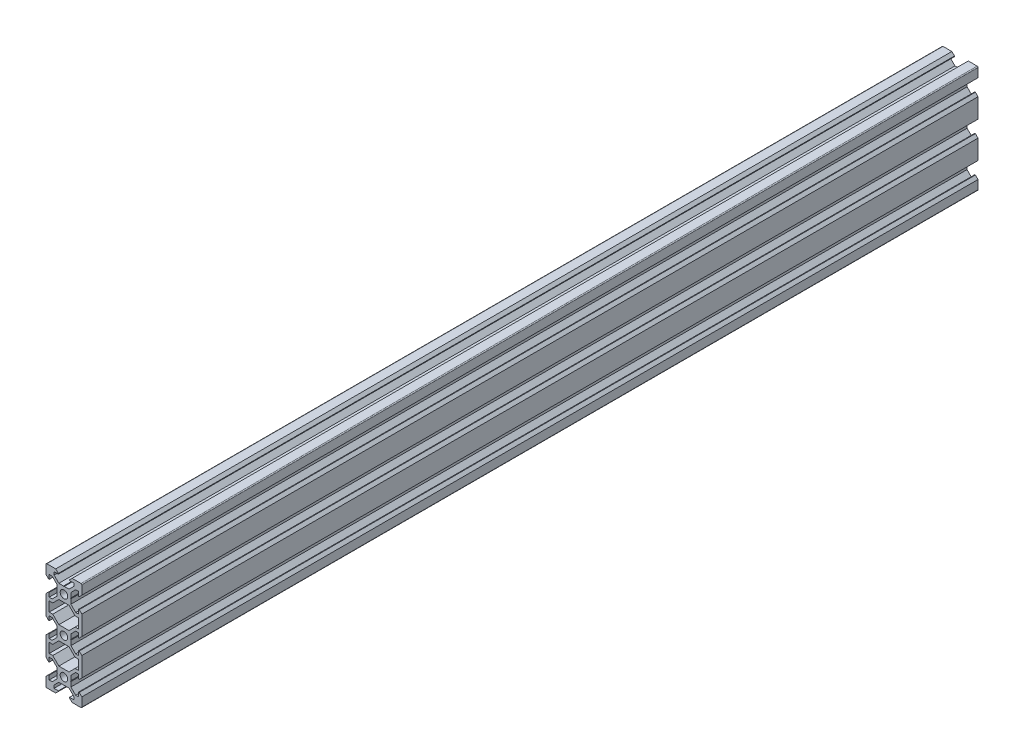
SolidWorks part; units mm, degrees
material "6061-T6 (SS)"
ref_plane "Front Plane" through (0, 0, 0) normal (0, 0, 1) x (1, 0, 0)
ref_plane "Top Plane" through (0, 0, 0) normal (0, 1, 0) x (1, 0, 0)
ref_plane "Right Plane" through (0, 0, 0) normal (1, 0, 0) x (0, 0, -1)
sketch "Sketch1" plane through (0, 0, 0) normal (0, 0, 1) x (1, 0, 0)
  line L0 (0, 0) -> (10, 0) construction
  line L1 (9.5, -30) -> (-9.5, -30)
  line L2 (10, -29.5) -> (10, 29.5)
  line L3 (9.5, 30) -> (-9.5, 30)
  line L4 (-10, -29.5) -> (-10, 29.5)
  line L5 (10, -30) -> (-10, 30) construction
  line L6 (10, 30) -> (-10, -30) construction
  circle A0 centre (0, 20) radius 2.1
  circle A1 centre (0, 0) radius 2.1
  circle A2 centre (0, -20) radius 2.1
  arc A3 (-9.5, -30) -> (-10, -29.5) centre (-9.5, -29.5) cw
  arc A4 (9.5, -30) -> (10, -29.5) centre (9.5, -29.5) ccw
  arc A5 (10, 29.5) -> (9.5, 30) centre (9.5, 29.5) ccw
  arc A6 (-9.5, 30) -> (-10, 29.5) centre (-9.5, 29.5) ccw
  point P0 (0, 0)
  line B0 (0, 20) -> (0, 30) construction
  line B1 (0, 23.69) -> (-0.21, 23.9)
  line B2 (-0.21, 23.9) -> (-2.8393, 23.9)
  line B3 (-2.8393, 23.9) -> (-5.5, 26.5607)
  line B4 (-5.5, 26.5607) -> (-5.5, 28.2)
  line B5 (-5.5, 28.2) -> (-3.125, 28.2)
  line B6 (-3.125, 28.2) -> (-3.125, 28.545)
  line B7 (-3.125, 28.545) -> (-4.58, 30)
  line B8 (-4.58, 30) -> (4.58, 30)
  line B9 (0, 20) -> (-5.9132, 25.9132) construction
  line B10 (3.125, 28.545) -> (4.58, 30)
  line B11 (3.125, 28.2) -> (3.125, 28.545)
  line B12 (5.5, 28.2) -> (3.125, 28.2)
  line B13 (5.5, 26.5607) -> (5.5, 28.2)
  line B14 (2.8393, 23.9) -> (5.5, 26.5607)
  line B15 (0.21, 23.9) -> (2.8393, 23.9)
  line B16 (0, 23.69) -> (0.21, 23.9)
  line B17 (0, 20) -> (-10, 20) construction
  line B18 (-3.69, 20) -> (-3.9, 19.79)
  line B19 (-3.9, 19.79) -> (-3.9, 17.1607)
  line B20 (-3.9, 17.1607) -> (-6.5607, 14.5)
  line B21 (-6.5607, 14.5) -> (-8.2, 14.5)
  line B22 (-8.2, 14.5) -> (-8.2, 16.875)
  line B23 (-8.2, 16.875) -> (-8.545, 16.875)
  line B24 (-8.545, 16.875) -> (-10, 15.42)
  line B25 (-10, 15.42) -> (-10, 24.58)
  line B26 (0, 20) -> (-5.9132, 14.0868) construction
  line B27 (-8.545, 23.125) -> (-10, 24.58)
  line B28 (-8.2, 23.125) -> (-8.545, 23.125)
  line B29 (-8.2, 25.5) -> (-8.2, 23.125)
  line B30 (-6.5607, 25.5) -> (-8.2, 25.5)
  line B31 (-3.9, 22.8393) -> (-6.5607, 25.5)
  line B32 (-3.9, 20.21) -> (-3.9, 22.8393)
  line B33 (-3.69, 20) -> (-3.9, 20.21)
  line B34 (0, 0) -> (-10, 0) construction
  line B35 (-3.69, 0) -> (-3.9, -0.21)
  line B36 (-3.9, -0.21) -> (-3.9, -2.8393)
  line B37 (-3.9, -2.8393) -> (-6.5607, -5.5)
  line B38 (-6.5607, -5.5) -> (-8.2, -5.5)
  line B39 (-8.2, -5.5) -> (-8.2, -3.125)
  line B40 (-8.2, -3.125) -> (-8.545, -3.125)
  line B41 (-8.545, -3.125) -> (-10, -4.58)
  line B42 (-10, -4.58) -> (-10, 4.58)
  line B43 (0, 0) -> (-5.9132, -5.9132) construction
  line B44 (-8.545, 3.125) -> (-10, 4.58)
  line B45 (-8.2, 3.125) -> (-8.545, 3.125)
  line B46 (-8.2, 5.5) -> (-8.2, 3.125)
  line B47 (-6.5607, 5.5) -> (-8.2, 5.5)
  line B48 (-3.9, 2.8393) -> (-6.5607, 5.5)
  line B49 (-3.9, 0.21) -> (-3.9, 2.8393)
  line B50 (-3.69, 0) -> (-3.9, 0.21)
  line B51 (0, -20) -> (-10, -20) construction
  line B52 (-3.69, -20) -> (-3.9, -20.21)
  line B53 (-3.9, -20.21) -> (-3.9, -22.8393)
  line B54 (-3.9, -22.8393) -> (-6.5607, -25.5)
  line B55 (-6.5607, -25.5) -> (-8.2, -25.5)
  line B56 (-8.2, -25.5) -> (-8.2, -23.125)
  line B57 (-8.2, -23.125) -> (-8.545, -23.125)
  line B58 (-8.545, -23.125) -> (-10, -24.58)
  line B59 (-10, -24.58) -> (-10, -15.42)
  line B60 (0, -20) -> (-5.9132, -25.9132) construction
  line B61 (-8.545, -16.875) -> (-10, -15.42)
  line B62 (-8.2, -16.875) -> (-8.545, -16.875)
  line B63 (-8.2, -14.5) -> (-8.2, -16.875)
  line B64 (-6.5607, -14.5) -> (-8.2, -14.5)
  line B65 (-3.9, -17.1607) -> (-6.5607, -14.5)
  line B66 (-3.9, -19.79) -> (-3.9, -17.1607)
  line B67 (-3.69, -20) -> (-3.9, -19.79)
  line B68 (0, -20) -> (0, -30) construction
  line B69 (0, -23.69) -> (0.21, -23.9)
  line B70 (0.21, -23.9) -> (2.8393, -23.9)
  line B71 (2.8393, -23.9) -> (5.5, -26.5607)
  line B72 (5.5, -26.5607) -> (5.5, -28.2)
  line B73 (5.5, -28.2) -> (3.125, -28.2)
  line B74 (3.125, -28.2) -> (3.125, -28.545)
  line B75 (3.125, -28.545) -> (4.58, -30)
  line B76 (4.58, -30) -> (-4.58, -30)
  line B77 (0, -20) -> (5.9132, -25.9132) construction
  line B78 (-3.125, -28.545) -> (-4.58, -30)
  line B79 (-3.125, -28.2) -> (-3.125, -28.545)
  line B80 (-5.5, -28.2) -> (-3.125, -28.2)
  line B81 (-5.5, -26.5607) -> (-5.5, -28.2)
  line B82 (-2.8393, -23.9) -> (-5.5, -26.5607)
  line B83 (-0.21, -23.9) -> (-2.8393, -23.9)
  line B84 (0, -23.69) -> (-0.21, -23.9)
  line B85 (0, -20) -> (10, -20) construction
  line B86 (3.69, -20) -> (3.9, -19.79)
  line B87 (3.9, -19.79) -> (3.9, -17.1607)
  line B88 (3.9, -17.1607) -> (6.5607, -14.5)
  line B89 (6.5607, -14.5) -> (8.2, -14.5)
  line B90 (8.2, -14.5) -> (8.2, -16.875)
  line B91 (8.2, -16.875) -> (8.545, -16.875)
  line B92 (8.545, -16.875) -> (10, -15.42)
  line B93 (10, -15.42) -> (10, -24.58)
  line B94 (0, -20) -> (5.9132, -14.0868) construction
  line B95 (8.545, -23.125) -> (10, -24.58)
  line B96 (8.2, -23.125) -> (8.545, -23.125)
  line B97 (8.2, -25.5) -> (8.2, -23.125)
  line B98 (6.5607, -25.5) -> (8.2, -25.5)
  line B99 (3.9, -22.8393) -> (6.5607, -25.5)
  line B100 (3.9, -20.21) -> (3.9, -22.8393)
  line B101 (3.69, -20) -> (3.9, -20.21)
  line B102 (0, 0) -> (10, 0) construction
  line B103 (3.69, 0) -> (3.9, 0.21)
  line B104 (3.9, 0.21) -> (3.9, 2.8393)
  line B105 (3.9, 2.8393) -> (6.5607, 5.5)
  line B106 (6.5607, 5.5) -> (8.2, 5.5)
  line B107 (8.2, 5.5) -> (8.2, 3.125)
  line B108 (8.2, 3.125) -> (8.545, 3.125)
  line B109 (8.545, 3.125) -> (10, 4.58)
  line B110 (10, 4.58) -> (10, -4.58)
  line B111 (0, 0) -> (5.9132, 5.9132) construction
  line B112 (8.545, -3.125) -> (10, -4.58)
  line B113 (8.2, -3.125) -> (8.545, -3.125)
  line B114 (8.2, -5.5) -> (8.2, -3.125)
  line B115 (6.5607, -5.5) -> (8.2, -5.5)
  line B116 (3.9, -2.8393) -> (6.5607, -5.5)
  line B117 (3.9, -0.21) -> (3.9, -2.8393)
  line B118 (3.69, 0) -> (3.9, -0.21)
  line B119 (0, 20) -> (10, 20) construction
  line B120 (3.69, 20) -> (3.9, 20.21)
  line B121 (3.9, 20.21) -> (3.9, 22.8393)
  line B122 (3.9, 22.8393) -> (6.5607, 25.5)
  line B123 (6.5607, 25.5) -> (8.2, 25.5)
  line B124 (8.2, 25.5) -> (8.2, 23.125)
  line B125 (8.2, 23.125) -> (8.545, 23.125)
  line B126 (8.545, 23.125) -> (10, 24.58)
  line B127 (10, 24.58) -> (10, 15.42)
  line B128 (0, 20) -> (5.9132, 25.9132) construction
  line B129 (8.545, 16.875) -> (10, 15.42)
  line B130 (8.2, 16.875) -> (8.545, 16.875)
  line B131 (8.2, 14.5) -> (8.2, 16.875)
  line B132 (6.5607, 14.5) -> (8.2, 14.5)
  line B133 (3.9, 17.1607) -> (6.5607, 14.5)
  line B134 (3.9, 19.79) -> (3.9, 17.1607)
  line B135 (3.69, 20) -> (3.9, 19.79)
  line B136 (-8.2, 7.3) -> (-8.2, 12.7)
  line B137 (-8.2, 12.7) -> (-6.2393, 12.7)
  line B138 (-6.2393, 12.7) -> (-2.8393, 16.1)
  line B139 (-2.8393, 16.1) -> (2.8393, 16.1)
  line B140 (0, 16.1) -> (0, 10) construction
  line B141 (0, 10) -> (-8.2, 10) construction
  line B142 (6.2393, 12.7) -> (2.8393, 16.1)
  line B143 (8.2, 12.7) -> (6.2393, 12.7)
  line B144 (8.2, 7.3) -> (8.2, 12.7)
  line B145 (8.2, 7.3) -> (6.2393, 7.3)
  line B146 (6.2393, 7.3) -> (2.8393, 3.9)
  line B147 (-2.8393, 3.9) -> (2.8393, 3.9)
  line B148 (-6.2393, 7.3) -> (-2.8393, 3.9)
  line B149 (-8.2, 7.3) -> (-6.2393, 7.3)
  line B150 (0, 16.1) -> (0, 20) construction
  line B151 (0, 20) -> (-5.0927, 14.9073) construction
  line B152 (-8.2, -12.7) -> (-8.2, -7.3)
  line B153 (-8.2, -7.3) -> (-6.2393, -7.3)
  line B154 (-6.2393, -7.3) -> (-2.8393, -3.9)
  line B155 (-2.8393, -3.9) -> (2.8393, -3.9)
  line B156 (0, -3.9) -> (0, -10) construction
  line B157 (0, -10) -> (-8.2, -10) construction
  line B158 (6.2393, -7.3) -> (2.8393, -3.9)
  line B159 (8.2, -7.3) -> (6.2393, -7.3)
  line B160 (8.2, -12.7) -> (8.2, -7.3)
  line B161 (8.2, -12.7) -> (6.2393, -12.7)
  line B162 (6.2393, -12.7) -> (2.8393, -16.1)
  line B163 (-2.8393, -16.1) -> (2.8393, -16.1)
  line B164 (-6.2393, -12.7) -> (-2.8393, -16.1)
  line B165 (-8.2, -12.7) -> (-6.2393, -12.7)
  line B166 (0, -3.9) -> (0, 0) construction
  line B167 (0, 0) -> (-5.0927, -5.0927) construction
  dimension "D3" = 4.2
  dimension "D5" = 0.5
  dimension "D1" = 20
  dimension "D2" = 60
  dimension "D4" = 40
sketch_block_instance "V Slot 1-4"
sketch_block "V Slot 1" parameters "D1"=10, "D2"=11, "D3"=4.3, "D4"=1.8, "D5"=0.21, "D6"=45, "D7"=9.16, "D8"=1.5, "D9"=6.25
sketch_block_instance "V Slot 1-5"
sketch_block_instance "V Slot 1-6"
sketch_block_instance "V Slot 1-7"
sketch_block_instance "V Slot 1-8"
sketch_block_instance "V Slot 1-9"
sketch_block_instance "V Slot 1-10"
sketch_block_instance "V Slot 1-11"
sketch_block_instance "Center Cutout 1-1"
sketch_block "Center Cutout 1" parameters "D1"=5.4, "D2"=12.2, "D3"=8.2, "D4"=45, "D5"=10, "D6"=1.5
sketch_block_instance "Center Cutout 1-2"
extrude "Boss-Extrude1" add sketch "Sketch1" along normal blind 500 contours B135 B120 B121 B122 B123 B124 B125 B126 L2 A5 L3 B10 B11 B12 B13 B14 B15 B16 B1 B2 B3 B4 B5 B6 B7 A6 L4 B27 B28 B29 B30 B31 B32 B33 B18 B19 B20 B21 B22 B23 B24 B44 B45 B46 B47 B48 B49 B50 B35 region at (7.04, -29.3675, 0)
